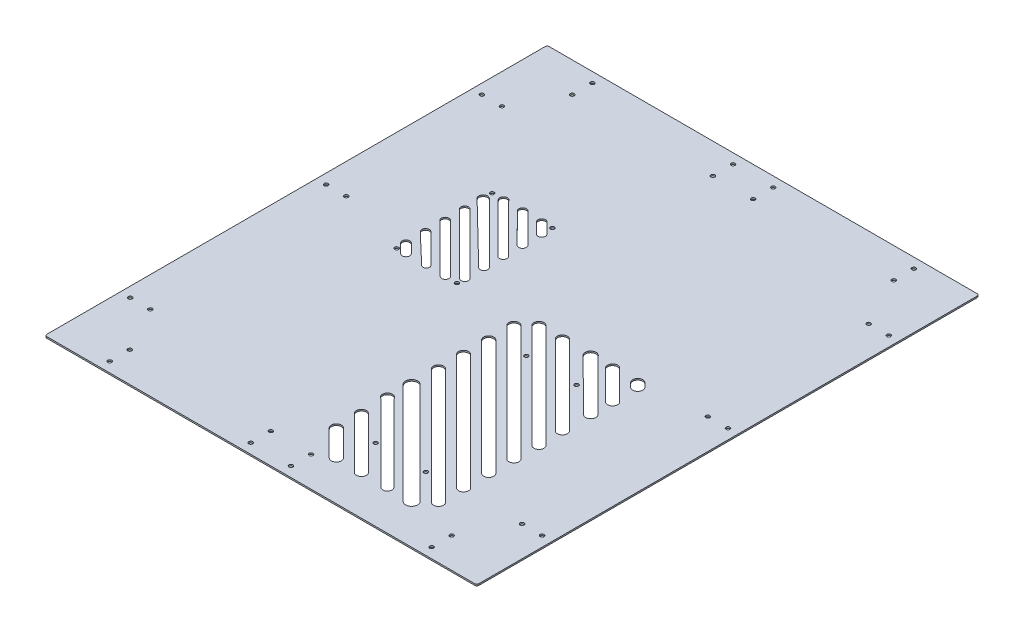
SolidWorks part; units mm, degrees
ref_plane "Front Plane" through (0, 0, 0) normal (0, 0, 1) x (1, 0, 0)
ref_plane "Top Plane" through (0, 0, 0) normal (0, 1, 0) x (1, 0, 0)
ref_plane "Right Plane" through (0, 0, 0) normal (1, 0, 0) x (0, 0, -1)
sketch "Sketch1" plane through (0, 0, 0) normal (0, 1, 0) x (1, 0, 0)
  line L1 (-215, -250) -> (215, -250)
  line L2 (-215, -250) -> (-215, 250)
  line L3 (-215, 250) -> (215, 250)
  line L4 (215, -250) -> (215, 250)
  line L5 (-215, -250) -> (215, 250) construction
  line L6 (-215, 250) -> (215, -250) construction
  point P0 (0, 0)
  dimension "D1" = 430
  dimension "D2" = 500
extrude "Boss-Extrude1" add sketch "Sketch1" along normal blind 1.5
sketch "Sketch6" plane through (0, 1.5, 0) normal (0, 1, 0) x (1, 0, 0)
  circle A0 centre (92.2927, -28) radius 1.95
  circle A1 centre (42.2927, -28) radius 1.95
  circle A2 centre (92.2927, -178) radius 1.95
  circle A3 centre (42.2927, -178) radius 1.95
  dimension "D1" = 50
  dimension "D2" = 150
sketch "Sketch7" plane through (0, 1.5, 0) normal (0, 1, 0) x (1, 0, 0)
  circle A0 centre (-114.98, 95.1924) radius 1.95
  circle A1 centre (-54.98, 95.1924) radius 1.95
  circle A2 centre (-54.98, 0.1924) radius 1.95
  circle A3 centre (-114.98, 0.1924) radius 1.95
  dimension "D1" = 95
  dimension "D2" = 60
sketch "Sketch12" plane through (0, 0, 0) normal (0, -1, 0) x (-1, 0, 0)
  line L0 (215, -250) -> (-215, -250) construction
  line L1 (-215, 250) -> (215, 250) construction
  line L2 (215, 250) -> (215, -250) construction
  line L3 (-215, -250) -> (-215, 250) construction
  circle A0 centre (-185, -175) radius 1.95
  circle A1 centre (-205, 170) radius 1.95
  circle A3 centre (-185, 10) radius 1.95
  circle A4 centre (-205, 10) radius 1.95
  circle A5 centre (-205, -175) radius 1.95
  circle A6 centre (-185, 170) radius 1.95
  circle A7 centre (205, -175) radius 1.95
  circle A8 centre (205, 20) radius 1.95
  circle A9 centre (185, 175) radius 1.95
  circle A10 centre (205, 175) radius 1.95
  circle A11 centre (185, -175) radius 1.95
  circle A12 centre (185, 20) radius 1.95
  circle A13 centre (160.3499, -240) radius 1.95
  circle A14 centre (160.3499, -220) radius 1.95
  circle A15 centre (20, -240) radius 1.95
  circle A16 centre (20, -220) radius 1.95
  circle A17 centre (-20, -220) radius 1.95
  circle A19 centre (-20, -240) radius 1.95
  circle A20 centre (-160, -240) radius 1.95
  circle A21 centre (-160, -220) radius 1.95
  circle A22 centre (160, 220) radius 1.95
  circle A23 centre (160, 240) radius 1.95
  circle A24 centre (20, 220) radius 1.95
  circle A25 centre (20, 240) radius 1.95
  circle A26 centre (-20, 220) radius 1.95
  circle A27 centre (-20, 240) radius 1.95
  circle A28 centre (-160, 220) radius 1.95
  circle A29 centre (-160, 240) radius 1.95
  dimension "D1" = 10
  dimension "D2" = 20
  dimension "D3" = 10
  dimension "D5" = 10
  dimension "D6" = 20
  dimension "D7" = 20
  dimension "D4" = 20
  dimension "D8" = 10
extrude "Cut-Extrude3" cut sketch "Sketch12" against normal blind 50.8
extrude "Cut-Extrude4" cut sketch "Sketch6" against normal blind 50.8
extrude "Cut-Extrude5" cut sketch "Sketch7" against normal blind 50.8
fillet "Fillet1" radius 2 4 edges at (215, 0.75, -250) (215, 0.75, 250) (-215, 0.75, 250) (-215, 0.75, -250)
sketch "Sketch13" plane through (0, 0, 0) normal (0, -1, 0) x (1, 0, 0)
  line L0 (67.2927, 28) -> (67.2927, 178) construction
  line L6 (92.2927, 178) -> (42.2927, 178) construction
  line L8 (92.2927, 178) -> (92.2927, 28) construction
  line L9 (92.2927, 28) -> (42.2927, 28) construction
  line L10 (42.2927, 178) -> (42.2927, 28) construction
  line L11 (67.2927, 103) -> (42.2927, 103) construction
  line L12 (124.7927, 122.9451) -> (9.7927, 7.9451) construction
  line L13 (124.7927, 210.5) -> (9.7927, 210.5)
  line L14 (124.7927, 210.5) -> (124.7927, -4.5)
  line L15 (124.7927, -4.5) -> (9.7927, -4.5)
  line L16 (9.7927, 210.5) -> (9.7927, -4.5)
  line L17 (124.7927, 210.5) -> (9.7927, -4.5) construction
  line L18 (124.7927, -4.5) -> (9.7927, 210.5) construction
  line L19 (128.3282, 119.4095) -> (13.3282, 4.4095)
  line L20 (121.2572, 126.4806) -> (6.2572, 11.4806)
  line L21 (124.7927, 147.9451) -> (9.7927, 32.9451) construction
  line L22 (128.3282, 144.4095) -> (13.3282, 29.4095)
  line L23 (121.2572, 151.4806) -> (6.2572, 36.4806)
  line L26 (124.7927, 172.9451) -> (9.7927, 57.9451) construction
  line L29 (128.3282, 169.4095) -> (13.3282, 54.4095)
  line L32 (121.2572, 176.4806) -> (6.2572, 61.4806)
  line L35 (124.7927, 197.9451) -> (9.7927, 82.9451) construction
  line L38 (128.3282, 194.4095) -> (13.3282, 79.4095)
  line L41 (121.2572, 201.4806) -> (6.2572, 86.4806)
  line L44 (110.6506, 210.5) -> (9.7927, 109.6421) construction
  line L47 (114.8916, 206.259) -> (14.0337, 105.4011)
  line L50 (102.1686, 210.5) -> (5.5517, 113.8831)
  line L53 (-54.98, -95.1924) -> (-114.98, -95.1924) construction
  line L58 (-114.98, -95.1924) -> (-114.98, -44.2867) construction
  line L62 (86.5307, 210.5) -> (8.6916, 132.661) construction
  line L65 (-114.98, -0.1924) -> (-54.98, -0.1924) construction
  line L66 (-54.98, -0.1924) -> (-54.98, -95.1924) construction
  line L67 (-54.98, -84.5868) -> (-65.5855, -95.1924) construction
  line L68 (-54.98, -89.8901) -> (-60.2822, -95.1924)
  line L69 (-57.6303, -81.9365) -> (-68.2358, -92.5421)
  line L70 (-54.98, -95.1924) -> (-114.98, -0.1924) construction
  line L71 (-54.98, -65.4331) -> (-84.7393, -95.1924) construction
  line L72 (-54.98, -70.7364) -> (-79.4324, -95.1924)
  line L73 (-57.6384, -62.7886) -> (-87.2428, -92.5491)
  line L74 (-54.98, -46.2793) -> (-103.893, -95.1924) construction
  line L75 (-54.98, -51.5826) -> (-98.5897, -95.1924)
  line L76 (-57.6398, -43.6363) -> (-106.2442, -92.5505)
  line L77 (-54.98, -27.1256) -> (-120.2706, -91.5396) construction
  line L78 (-54.98, -32.4289) -> (-111.9255, -89.3745)
  line L79 (-57.5955, -24.4383) -> (-117.9928, -83.2246)
  line L80 (-52.4189, -5.4139) -> (-114.98, -67.9718) construction
  line L81 (-52.3742, -10.6694) -> (-112.3283, -70.6235)
  line L83 (-63.9533, 2.3637) -> (-114.98, -48.8181) construction
  line L84 (-63.9494, -2.7446) -> (-112.3283, -51.1235)
  line L87 (-71.6576, -0.1924) -> (-114.98, -43.5148)
  line L88 (-85.508, -0.1924) -> (-114.98, -29.6644) construction
  line L91 (-83.2026, -2.4978) -> (-112.3283, -31.6235)
  line L92 (-90.2324, -0.1924) -> (-114.98, -23.7903)
  line L93 (-105.7005, -0.1924) -> (-114.98, -10.5106) construction
  line L96 (-103.0489, -2.844) -> (-112.3283, -12.1235)
  line L99 (-111.0038, -0.1924) -> (-114.98, -4.1685)
  line L102 (-60.2822, -95.1924) -> (-62.9366, -97.844)
  line L105 (-98.5897, -95.1924) -> (-100.7736, -97.6705)
  line L106 (-79.4324, -95.1924) -> (-81.8594, -97.7646)
  line L107 (-114.98, -62.6685) -> (-117.6316, -65.3202)
  line L108 (-114.98, -43.5148) -> (-117.4324, -45.635)
  line L109 (-114.98, -4.1685) -> (-117.6316, -6.8202)
  line L110 (-54.98, -89.8901) -> (-52.3283, -87.2358)
  line L111 (-54.98, -70.7364) -> (-52.3283, -68.0843)
  line L112 (-54.98, -51.5826) -> (-52.3283, -48.9306)
  line L113 (-54.98, -32.4289) -> (-52.3283, -29.7772)
  line L114 (-57.5857, -5.4578) -> (-114.98, -62.6685)
  line L115 (-90.2324, -0.1924) -> (-87.7579, 2.1672)
  line L116 (-71.6576, -0.1924) -> (-69.0283, 2.3851)
  line L117 (-111.0038, -0.1924) -> (-108.3522, 2.4593)
  line L118 (-114.98, -23.7903) -> (-117.5678, -26.2579)
  line L119 (89.7127, 207.318) -> (13.4147, 131.0201)
  line L120 (80.1667, 210.5) -> (7.0508, 137.3841)
  line L121 (60.6506, 210.5) -> (9.7927, 159.6421) construction
  line L122 (64.1861, 206.9645) -> (13.3282, 156.1066)
  line L123 (53.5795, 210.5) -> (6.2572, 163.1777)
  line L124 (35.6506, 210.5) -> (9.7927, 184.6421) construction
  line L125 (39.1861, 206.9645) -> (13.3282, 181.1066)
  line L126 (28.5795, 210.5) -> (6.2572, 188.1777)
  line L127 (10.6506, 210.5) -> (9.7927, 209.6421) construction
  line L128 (16.6674, 209.4458) -> (13.3282, 206.1066)
  line L130 (128.3284, -3.8936) -> (124.1859, -8.0357)
  line L133 (125.6429, 98.792) -> (22.3509, -4.5) construction
  line L134 (129.1784, 95.2564) -> (29.422, -4.5)
  line L135 (122.1073, 102.3275) -> (18.8154, -0.9645)
  line L136 (124.7927, 74.6421) -> (45.6506, -4.5) construction
  line L137 (128.3282, 71.1066) -> (52.7216, -4.5)
  line L138 (121.2572, 78.1777) -> (42.115, -0.9645)
  line L139 (124.7927, 46.436) -> (73.8567, -4.5) construction
  line L140 (128.4341, 42.7783) -> (80.9436, -4.5)
  line L141 (121.1513, 50.0937) -> (70.1015, -0.728)
  line L142 (124.7927, 24.6421) -> (95.6506, -4.5) construction
  line L143 (128.3282, 21.1066) -> (102.7216, -4.5)
  line L144 (121.2572, 28.1777) -> (92.115, -0.9645)
  line L145 (124.7928, -0.358) -> (120.6506, -4.5) construction
  line L147 (121.2572, 3.1777) -> (117.115, -0.9645)
  line L166 (6.6802, 213.5553) -> (10.376, 216.4949)
  line L167 (28.5795, 210.5) -> (32.115, 214.0355)
  line L168 (53.5795, 210.5) -> (57.115, 214.0355)
  line L169 (80.1667, 210.5) -> (83.3487, 213.682)
  line L170 (102.1686, 210.5) -> (106.4096, 214.741)
  line L171 (102.7216, -4.5) -> (99.1861, -8.0355)
  line L172 (80.9436, -4.5) -> (77.854, -8.0143)
  line L173 (52.7216, -4.5) -> (49.1861, -8.0355)
  line L174 (29.422, -4.5) -> (25.8864, -8.0355)
  line L356 (124.7927, 347.9451) -> (9.7927, 232.9451) construction
  line L357 (128.3282, 344.4095) -> (13.3282, 229.4095) [skipped]
  line L358 (121.2572, 351.4806) -> (6.2572, 236.4806) [skipped]
  line L359 (124.7927, 322.9451) -> (9.7927, 207.9451) construction
  line L360 (128.3282, 319.4095) -> (13.3282, 204.4095) [skipped]
  line L361 (121.2572, 326.4806) -> (6.2572, 211.4806) [skipped]
  line L362 (124.7927, 297.9451) -> (9.7927, 182.9451) construction
  line L363 (128.3282, 294.4095) -> (13.3282, 179.4095) [skipped]
  line L364 (121.2572, 301.4806) -> (6.2572, 186.4806) [skipped]
  line L365 (124.7927, 272.9451) -> (9.7927, 157.9451) construction
  line L366 (128.3282, 269.4095) -> (13.3282, 154.4095) [skipped]
  line L367 (121.2572, 276.4806) -> (6.2572, 161.4806) [skipped]
  line L368 (124.7927, 247.9451) -> (9.7927, 132.9451) construction
  line L369 (128.3282, 244.4095) -> (13.3282, 129.4095) [skipped]
  line L370 (121.2572, 251.4806) -> (6.2572, 136.4806) [skipped]
  line L371 (124.7927, 222.9451) -> (9.7927, 107.9451) construction
  line L372 (128.3282, 219.4095) -> (13.3282, 104.4095) [skipped]
  line L373 (121.2572, 226.4806) -> (6.2572, 111.4806) [skipped]
  line L374 (124.7927, 347.9451) -> (9.7927, 232.9451) construction
  line L375 (128.3282, 344.4095) -> (13.3282, 229.4095) [skipped]
  line L376 (121.2572, 351.4806) -> (6.2572, 236.4806) [skipped]
  line L377 (124.7927, 322.9451) -> (9.7927, 207.9451) construction
  line L378 (128.3282, 319.4095) -> (13.3282, 204.4095) [skipped]
  line L379 (121.2572, 326.4806) -> (6.2572, 211.4806) [skipped]
  line L380 (124.7927, 297.9451) -> (9.7927, 182.9451) construction
  line L381 (128.3282, 294.4095) -> (13.3282, 179.4095) [skipped]
  line L382 (121.2572, 301.4806) -> (6.2572, 186.4806) [skipped]
  line L383 (124.7927, 272.9451) -> (9.7927, 157.9451) construction
  line L384 (128.3282, 269.4095) -> (13.3282, 154.4095) [skipped]
  line L385 (121.2572, 276.4806) -> (6.2572, 161.4806) [skipped]
  line L386 (124.7927, 247.9451) -> (9.7927, 132.9451) construction
  line L387 (128.3282, 244.4095) -> (13.3282, 129.4095) [skipped]
  line L388 (121.2572, 251.4806) -> (6.2572, 136.4806) [skipped]
  line L389 (124.7927, 222.9451) -> (9.7927, 107.9451) construction
  line L390 (128.3282, 219.4095) -> (13.3282, 104.4095) [skipped]
  line L391 (121.2572, 226.4806) -> (6.2572, 111.4806) [skipped]
  arc A32 (128.3282, 119.4095) -> (121.2572, 126.4806) centre (124.7927, 122.9451) ccw
  arc A59 (-68.2358, -92.5421) -> (-62.9366, -97.844) centre (-65.5855, -95.1924) ccw
  arc A60 (-87.2428, -92.5491) -> (-81.8594, -97.7646) centre (-84.5855, -95.1924) ccw
  arc A61 (-106.2442, -92.5505) -> (-100.7736, -97.6705) centre (-103.5855, -95.1924) ccw
  arc A63 (-117.6316, -65.3202) -> (-112.3283, -70.6235) centre (-114.98, -67.9718) ccw
  arc A64 (-117.4324, -45.635) -> (-112.3283, -51.1235) centre (-114.98, -48.4718) ccw
  arc A65 (-117.5678, -26.2579) -> (-112.3283, -31.6235) centre (-114.98, -28.9718) ccw
  arc A66 (-117.6316, -6.8202) -> (-112.3283, -12.1235) centre (-114.98, -9.4718) ccw
  arc A67 (-52.3283, -29.7772) -> (-57.5955, -24.4383) centre (-54.98, -27.1256) ccw
  arc A68 (-52.3283, -48.9306) -> (-57.6398, -43.6363) centre (-54.98, -46.2793) ccw
  arc A69 (-52.3283, -68.0843) -> (-57.6384, -62.7886) centre (-54.98, -65.4331) ccw
  arc A70 (-52.3283, -87.2358) -> (-57.6303, -81.9365) centre (-54.98, -84.5868) ccw
  arc A71 (-52.3742, -10.6694) -> (-57.5857, -5.4578) centre (-54.98, -8.0636) ccw
  arc A72 (-117.9928, -83.2246) -> (-111.9255, -89.3745) centre (-114.98, -86.32) ccw
  arc A73 (6.2572, 11.4806) -> (13.3282, 4.4095) centre (9.7927, 7.9451) ccw
  arc A74 (128.3282, 144.4095) -> (121.2572, 151.4806) centre (124.7927, 147.9451) ccw
  arc A75 (6.2572, 36.4806) -> (13.3282, 29.4095) centre (9.7927, 32.9451) ccw
  arc A76 (128.3282, 169.4095) -> (121.2572, 176.4806) centre (124.7927, 172.9451) ccw
  arc A77 (6.2572, 61.4806) -> (13.3282, 54.4095) centre (9.7927, 57.9451) ccw
  circle A78 centre (-122.5855, -95.1924) radius 3.7481 [skipped]
  arc A79 (-83.2026, -2.4978) -> (-87.7579, 2.1672) centre (-85.508, -0.1924) ccw
  arc A80 (-103.0489, -2.844) -> (-108.3522, 2.4593) centre (-105.7005, -0.1924) ccw
  arc A81 (-63.9494, -2.7446) -> (-69.0283, 2.3851) centre (-66.5016, -0.1924) ccw
  arc A82 (128.3282, 194.4095) -> (121.2572, 201.4806) centre (124.7927, 197.9451) ccw
  arc A83 (6.2572, 86.4806) -> (13.3282, 79.4095) centre (9.7927, 82.9451) ccw
  arc A85 (5.5517, 113.8831) -> (14.0337, 105.4011) centre (9.7927, 109.6421) ccw
  arc A87 (7.0508, 137.3841) -> (13.4147, 131.0201) centre (8.6916, 132.661) ccw
  arc A89 (6.2572, 163.1777) -> (13.3282, 156.1066) centre (9.7927, 159.6421) ccw
  arc A91 (6.2572, 188.1777) -> (13.3282, 181.1066) centre (9.7927, 184.6421) ccw
  arc A93 (6.6802, 213.5553) -> (13.3282, 206.1066) centre (9.7927, 209.6421) ccw
  arc A96 (129.1784, 95.2564) -> (122.1073, 102.3275) centre (125.6429, 98.792) ccw
  arc A98 (128.3282, 71.1066) -> (121.2572, 78.1777) centre (124.7927, 74.6421) ccw
  arc A100 (128.4341, 42.7783) -> (121.1513, 50.0937) centre (124.7927, 46.436) ccw
  arc A102 (128.3282, 21.1066) -> (121.2572, 28.1777) centre (124.7927, 24.6421) ccw
  arc A104 (128.3284, -3.8936) -> (121.2572, 3.1777) centre (124.7928, -0.358) ccw
  arc A118 (117.115, -0.9645) -> (124.1859, -8.0357) centre (120.6506, -4.5) ccw
  arc A119 (92.115, -0.9645) -> (99.1861, -8.0355) centre (95.6506, -4.5) ccw
  arc A120 (70.1015, -0.728) -> (77.854, -8.0143) centre (73.8567, -4.5) ccw
  arc A121 (42.115, -0.9645) -> (49.1861, -8.0355) centre (45.6506, -4.5) ccw
  arc A122 (18.8154, -0.9645) -> (25.8864, -8.0355) centre (22.3509, -4.5) ccw
  arc A123 (114.8916, 206.259) -> (106.4096, 214.741) centre (110.6506, 210.5) ccw
  arc A124 (89.7127, 207.318) -> (83.3487, 213.682) centre (86.5307, 210.5) ccw
  arc A125 (64.1861, 206.9645) -> (57.115, 214.0355) centre (60.6506, 210.5) ccw
  arc A126 (39.1861, 206.9645) -> (32.115, 214.0355) centre (35.6506, 210.5) ccw
  arc A127 (16.6674, 209.4458) -> (10.376, 216.4949) centre (13.3216, 212.7917) ccw
  arc A261 (128.3282, 344.4095) -> (121.2572, 351.4806) centre (124.7927, 347.9451) ccw [skipped]
  arc A262 (6.2572, 236.4806) -> (13.3282, 229.4095) centre (9.7927, 232.9451) ccw [skipped]
  arc A263 (128.3282, 319.4095) -> (121.2572, 326.4806) centre (124.7927, 322.9451) ccw [skipped]
  arc A264 (6.2572, 211.4806) -> (13.3282, 204.4095) centre (9.7927, 207.9451) ccw [skipped]
  arc A265 (128.3282, 294.4095) -> (121.2572, 301.4806) centre (124.7927, 297.9451) ccw [skipped]
  arc A266 (6.2572, 186.4806) -> (13.3282, 179.4095) centre (9.7927, 182.9451) ccw [skipped]
  arc A267 (128.3282, 269.4095) -> (121.2572, 276.4806) centre (124.7927, 272.9451) ccw [skipped]
  arc A268 (6.2572, 161.4806) -> (13.3282, 154.4095) centre (9.7927, 157.9451) ccw [skipped]
  arc A269 (128.3282, 244.4095) -> (121.2572, 251.4806) centre (124.7927, 247.9451) ccw [skipped]
  arc A270 (6.2572, 136.4806) -> (13.3282, 129.4095) centre (9.7927, 132.9451) ccw [skipped]
  arc A271 (128.3282, 219.4095) -> (121.2572, 226.4806) centre (124.7927, 222.9451) ccw [skipped]
  arc A272 (6.2572, 111.4806) -> (13.3282, 104.4095) centre (9.7927, 107.9451) ccw [skipped]
  point P2 (85.6506, 210.5)
  point P3 (85.6506, 210.5)
  point P18 (67.2927, 65.4451)
  point P23 (67.2927, 90.4451)
  point P30 (67.2927, 115.4451)
  point P37 (67.2927, 140.4451)
  point P46 (67.2927, 167.1421)
  point P54 (67.2927, 192.1421)
  point P55 (0, 0)
  point P61 (124.7927, 45.8759)
  point P62 (0, 0)
  point P69 (70.7597, -4.5)
  point P73 (67.2927, 217.1421)
  point P85 (67.2927, 153)
  point P89 (-59.0853, -88.6922)
  point P94 (67.2927, 42.1421)
  point P102 (67.2927, 17.1421)
  point P116 (67.2927, 193)
  point P124 (-66.4512, -76.9043)
  point P125 (67.2927, 173)
  point P135 (-73.8171, -65.1165)
  point P151 (-81.183, -53.3286)
  point P153 (67.2927, 193)
  point P156 (67.2927, 292.1421)
  point P159 (-88.5489, -41.5407)
  point P160 (67.2927, 173)
  point P167 (67.2927, 153)
  point P168 (-95.9147, -29.7529)
  point P174 (67.2927, 193)
  point P176 (-103.2806, -17.965)
  point P181 (67.2927, 173)
  point P184 (-110.6465, -6.1771)
  point P188 (67.2927, 153)
  point P207 (67.2927, 267.1421)
  point P227 (67.2927, 242.1421)
  point P235 (67.2927, 192.1421)
  point P242 (67.2927, 167.1421)
  point P251 (67.2927, 193)
  point P258 (67.2927, 173)
  point P265 (67.2927, 153)
  point P272 (67.2927, 193)
  point P279 (67.2927, 173)
  point P286 (67.2927, 153)
  point P321 (67.2927, 193)
  point P328 (67.2927, 173)
  point P335 (67.2927, 153)
  point P342 (67.2927, 193)
  point P349 (67.2927, 173)
  point P356 (67.2927, 153)
  point P365 (67.2927, 193)
  point P372 (67.2927, 173)
  point P379 (67.2927, 153)
  point P386 (67.2927, 193)
  point P393 (67.2927, 173)
  point P400 (67.2927, 153)
  point P407 (67.2927, 193)
  point P414 (67.2927, 173)
  point P421 (67.2927, 153)
  point P428 (67.2927, 193)
  point P435 (67.2927, 173)
  point P442 (67.2927, 153)
  point P449 (67.2927, 193)
  point P456 (67.2927, 173)
  point P463 (67.2927, 153)
  point P470 (67.2927, 193)
  point P477 (67.2927, 173)
  point P484 (67.2927, 153)
  point P491 (67.2927, 193)
  point P498 (67.2927, 173)
  point P505 (67.2927, 153)
  point P512 (67.2927, 193)
  point P519 (67.2927, 173)
  point P526 (67.2927, 153)
  point P533 (67.2927, 193)
  point P540 (67.2927, 173)
  point P547 (67.2927, 153)
  point P554 (67.2927, 193)
  point P561 (67.2927, 173)
  point P568 (67.2927, 153)
  point P575 (67.2927, 193)
  point P582 (67.2927, 173)
  point P589 (67.2927, 153)
  point P596 (67.2927, 193)
  point P603 (67.2927, 173)
  point P610 (67.2927, 153)
  point P617 (67.2927, 193)
  point P624 (67.2927, 173)
  point P631 (67.2927, 153)
  point P638 (67.2927, 193)
  point P645 (67.2927, 173)
  point P652 (67.2927, 153)
  point P677 (67.2927, 292.1421)
  point P684 (67.2927, 267.1421)
  point P691 (67.2927, 242.1421)
  point P698 (67.2927, 217.1421)
  point P705 (67.2927, 192.1421)
  point P712 (67.2927, 167.1421)
  point P719 (67.2927, 288.6066)
  point P726 (67.2927, 263.6066)
  point P733 (67.2927, 238.6066)
  point P740 (67.2927, 213.6066)
  point P747 (67.2927, 188.6066)
  point P754 (67.2927, 163.6066)
  point P761 (67.2927, 288.6066)
  point P768 (67.2927, 263.6066)
  point P775 (67.2927, 238.6066)
  point P782 (67.2927, 213.6066)
  point P789 (67.2927, 188.6066)
  point P796 (67.2927, 163.6066)
  point P803 (67.2927, 288.6066)
  point P810 (67.2927, 263.6066)
  point P817 (67.2927, 238.6066)
  point P824 (67.2927, 213.6066)
  point P831 (67.2927, 188.6066)
  point P838 (67.2927, 163.6066)
  point P845 (67.2927, 288.6066)
  point P852 (67.2927, 263.6066)
  point P859 (67.2927, 238.6066)
  point P866 (67.2927, 213.6066)
  point P873 (67.2927, 188.6066)
  point P880 (67.2927, 163.6066)
  point P887 (67.2927, 288.6066)
  point P894 (67.2927, 263.6066)
  point P901 (67.2927, 238.6066)
  point P908 (67.2927, 213.6066)
  point P915 (67.2927, 188.6066)
  point P922 (67.2927, 163.6066)
  point P929 (67.2927, 288.6066)
  point P936 (67.2927, 263.6066)
  point P943 (67.2927, 238.6066)
  point P950 (67.2927, 213.6066)
  point P957 (67.2927, 188.6066)
  point P964 (67.2927, 163.6066)
  point P971 (67.2927, 289.3137)
  point P978 (67.2927, 264.3137)
  point P985 (67.2927, 239.3137)
  point P992 (67.2927, 214.3137)
  point P999 (67.2927, 189.3137)
  point P1006 (67.2927, 164.3137)
  point P1013 (67.2927, 289.3137)
  point P1020 (67.2927, 264.3137)
  point P1027 (67.2927, 239.3137)
  point P1034 (67.2927, 214.3137)
  point P1041 (67.2927, 189.3137)
  point P1048 (67.2927, 164.3137)
  point P1055 (67.2927, 290.4451)
  point P1062 (67.2927, 265.4451)
  point P1069 (67.2927, 240.4451)
  point P1076 (67.2927, 215.4451)
  point P1083 (67.2927, 190.4451)
  point P1090 (67.2927, 165.4451)
  point P1097 (67.2927, 290.4451)
  point P1104 (67.2927, 265.4451)
  point P1111 (67.2927, 240.4451)
  point P1118 (67.2927, 215.4451)
  point P1125 (67.2927, 190.4451)
  point P1132 (67.2927, 165.4451)
  point P1139 (67.2927, 290.4451)
  point P1146 (67.2927, 265.4451)
  point P1153 (67.2927, 240.4451)
  point P1160 (67.2927, 215.4451)
  point P1167 (67.2927, 190.4451)
  point P1174 (67.2927, 165.4451)
  dimension "D1" = 115
  dimension "D5" = 45
  dimension "D6" = 4
  dimension "D7" = 4
  dimension "D8" = 45
  dimension "D9" = 3.8
  dimension "D10" = 10
  dimension "D2" = 215
  dimension "D3" = 45
  dimension "D4" = 5
  dimension "D11" = 7.68
  dimension "D12" = 10
  dimension "D13" = 9
  dimension "D14" = 45
  dimension "D15" = 45
  dimension "D16" = 5
  dimension "D17" = 3.8
extrude "Cut-Extrude6" cut sketch "Sketch13" against normal blind 10 contours L69 A59 L102 L68 L110 A70 | A69 L73 A60 L106 L72 L111 | L75 L105 A61 L76 A68 L112 | A67 L79 A72 L78 L113 | L81 A63 L107 L114 A71 | L108 A64 L84 A81 L116 L87 | A65 L91 A79 L115 L92 L118 | L96 A66 L109 L99 L117 A80 | A125 L168 L123 A89 L122 | A126 L167 L126 A91 L125 | L119 A87 L120 L169 A124 | A123 L170 L50 A85 L47 | L38 A83 L41 A82 | L29 A77 L32 A76 | L22 A75 L23 A74 | L20 A73 L19 A32 | L135 A122 L174 L134 A96 | L138 A121 L173 L137 A98 | L141 A120 L172 L140 A100 | L144 A119 L171 L143 A102 | L147 A118 L130 A104
